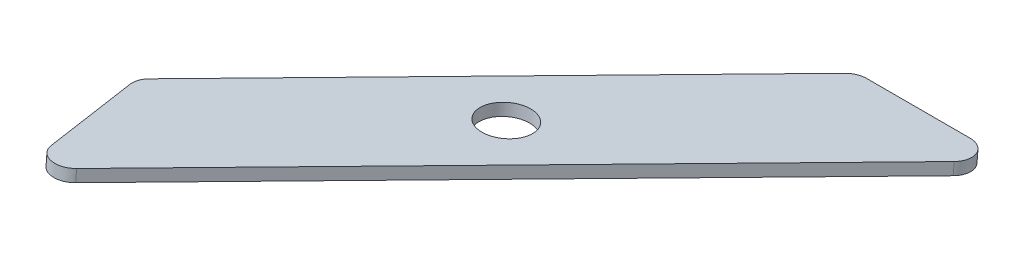
SolidWorks part; units mm, degrees
note: '?' marks a value the reader was unsure of.
material "Plain Carbon Steel"
ref_plane "Front Plane" through (0, 0, 0) normal (0, 0, 1) x (1, 0, 0)
ref_plane "Top Plane" through (0, 0, 0) normal (0, 1, 0) x (1, 0, 0)
ref_plane "Right Plane" through (0, 0, 0) normal (1, 0, 0) x (0, 0, -1)
ref_axis "Axis1" through (323.2409, 73.7808, 63.5779) along (-0.2127, 0.0811, 0.9737)?
ref_axis "Axis2" through (-330.1109, 71.1626, 32.129) along (0.2127, 0.0811, 0.9737)?
ref_axis "Axis3" through (330.2, 71.12, 29.2862) along (-1, 0, 0)?
ref_plane "Plane1" through (0, 68.0164, -5.6624) normal (0, -0.9966, 0.083) x (-1, 0, 0)
ref_plane "Plane2" through (0, 55.3602, -4.6088) normal (0, -0.9966, 0.083) x (-1, 0, 0)
sketch "Sketch2" plane through (0, 55.3602, -4.6088) normal (0, -0.9966, 0.083) x (-1, 0, 0)
  line L0 (255.5477, -35.0856) -> (314.7364, -108.5458)
  line L1 (-330.2, -35.0856) -> (330.2, -35.0856) construction
  line L2 (330.1109, -37.9221) -> (200.3407, -634.0279) construction
  line L3 (314.7364, -108.5458) -> (319.0729, -88.6255)
  line L4 (319.0729, -88.6255) -> (275.9345, -35.0856)
  line L5 (275.9345, -35.0856) -> (255.5477, -35.0856)
  line L6 (265.7411, -35.0856) -> (316.9047, -98.5856) construction
  line L7 (314.7364, -108.5458) -> (275.9345, -35.0856) construction
  line L8 (255.5477, -35.0856) -> (319.0729, -88.6255) construction
  circle A0 centre (291.3229, -66.8356) radius 3.2639
  dimension "D2" = 6.5278
  dimension "D3" = 31.75
  dimension "D1" = 15.875
extrude "Boss-Extrude1" add sketch "Sketch2" along normal blind 1.5875
fillet "Fillet1" radius 2.54 4 edges at (-275.9345, 57.4801, 30.4217) (-255.5477, 57.4801, 30.4217) (-319.0729, 61.9219, 83.777) (-314.7364, 63.5746, 103.6286)
